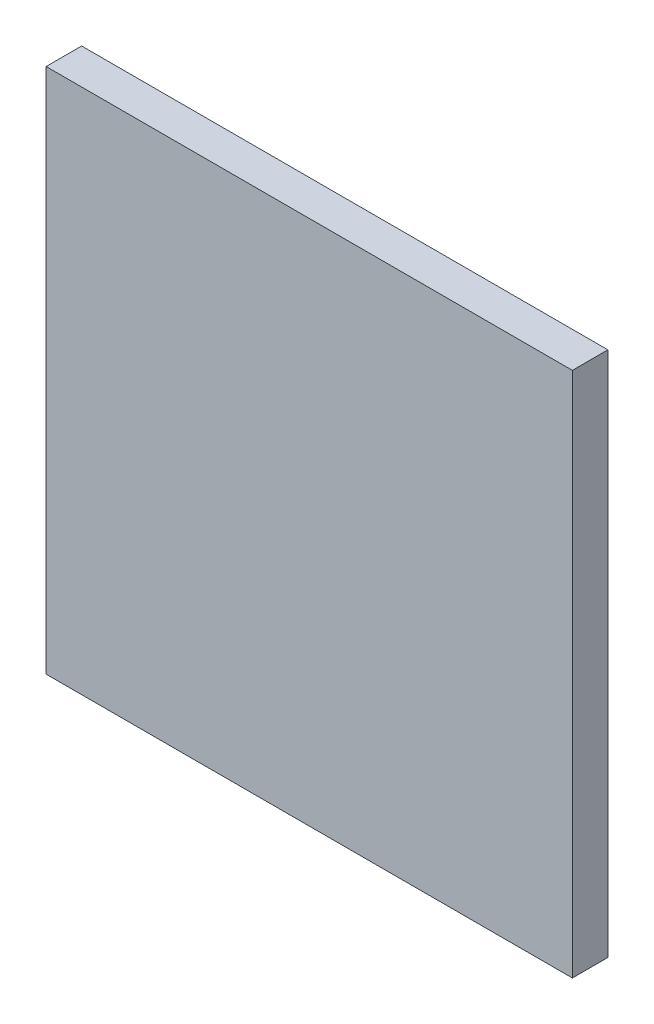
SolidWorks part; units mm, degrees
ref_plane "Front" through (0, 0, 0) normal (0, 0, 1) x (1, 0, 0)
ref_plane "Top" through (0, 0, 0) normal (0, 1, 0) x (1, 0, 0)
ref_plane "Right" through (0, 0, 0) normal (1, 0, 0) x (0, 0, -1)
sketch "Sketch1" plane through (0, 0, 0) normal (0, 0, 1) x (1, 0, 0)
  line L1 (22.225, 22.225) -> (-22.225, 22.225)
  line L2 (22.225, 22.225) -> (22.225, -22.225)
  line L3 (22.225, -22.225) -> (-22.225, -22.225)
  line L4 (-22.225, 22.225) -> (-22.225, -22.225)
extrude "Extrude1" add sketch "Sketch1" along normal blind 3
